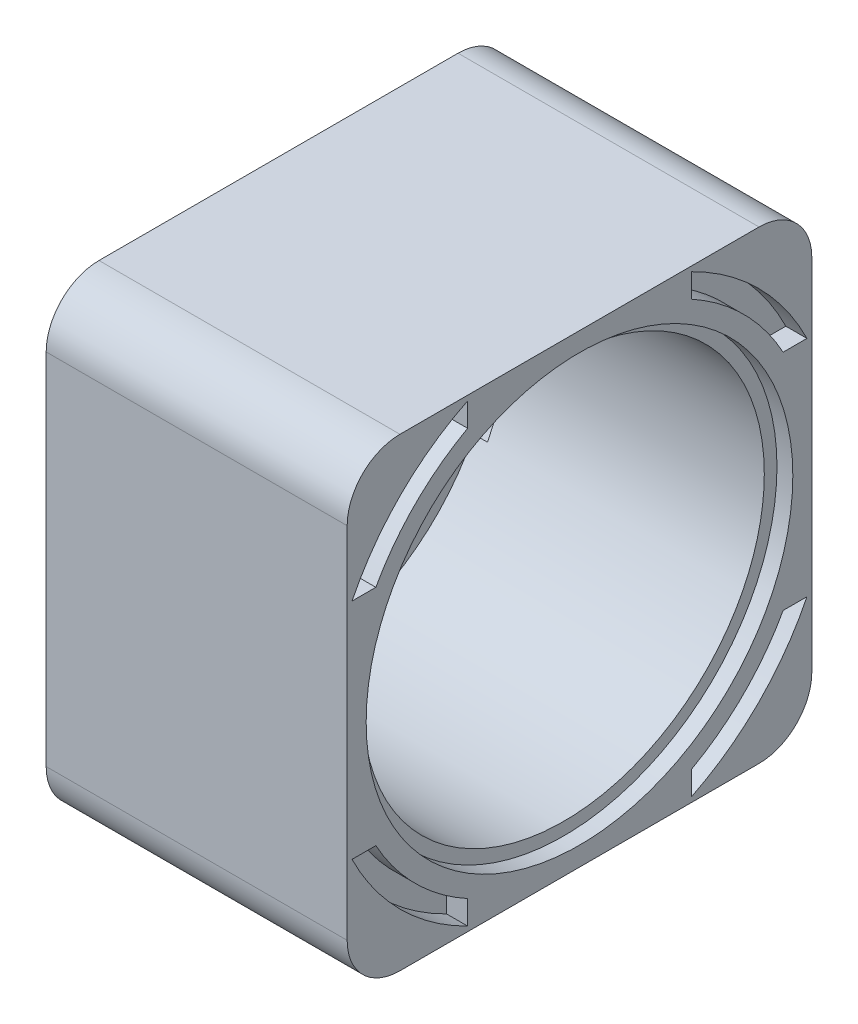
SolidWorks part; units mm, degrees
ref_plane "前视基准面" through (0, 0, 0) normal (0, 0, 1) x (1, 0, 0)
ref_plane "上视基准面" through (0, 0, 0) normal (0, 1, 0) x (1, 0, 0)
ref_plane "右视基准面" through (0, 0, 0) normal (1, 0, 0) x (0, 0, -1)
other "Configuration Table"
sketch "草图1" plane through (0, 0, 0) normal (1, 0, 0) x (0, 0, -1)
  line L6 (-22, 22) -> (22, 22)
  line L7 (-22, 22) -> (-22, -22)
  line L8 (-22, -22) -> (22, -22)
  line L9 (22, 22) -> (22, -22)
  line L10 (-22, 22) -> (22, -22) construction
  line L11 (-22, -22) -> (22, 22) construction
  point P0 (0, 0)
extrude "凸台-拉伸1" add sketch "草图1" along normal blind 1.5
sketch "草图2" plane through (1.5, 0, 0) normal (1, 0, 0) x (0, 0, -1)
  line L1 (0, 0) -> (5.5577, 0) construction
  circle A0 centre (0, 10.5) radius 1
  circle A1 centre (0, -10.5) radius 1
  circle A2 centre (0, -10.5) radius 2.5
  circle A5 centre (0, 10.5) radius 2.5
extrude "凸台-拉伸2" add sketch "草图2" along normal blind 3
sketch "草图3" plane through (1.5, 0, 0) normal (1, 0, 0) x (0, 0, -1)
  circle A0 centre (-12.5, -10.5) radius 2.5
  circle A1 centre (-12.5, -10.5) radius 1
  circle A2 centre (-12.5, 10.5) radius 1
  circle A3 centre (-12.5, 10.5) radius 2.5
extrude "凸台-拉伸3" add sketch "草图3" along normal blind 3.5
sketch "草图4" plane through (1.5, 0, 0) normal (1, 0, 0) x (0, 0, -1)
  line L5 (-22, 22) -> (22, 22)
  line L6 (-22, 22) -> (-22, -22)
  line L7 (-22, -22) -> (22, -22)
  line L8 (22, 22) -> (22, -22)
  line L9 (-22, 22) -> (22, -22) construction
  line L10 (-22, -22) -> (22, 22) construction
  circle A1 centre (0, 0) radius 19
extrude "凸台-拉伸4" add sketch "草图4" along normal blind 27
sketch "草图5" plane through (28.5, 0, 0) normal (1, 0, 0) x (0, 0, -1)
  circle A0 centre (0, 0) radius 20.2
  circle A1 centre (0, 0) radius 19
extrude "切除-拉伸1" cut sketch "草图5" against normal blind 1.5
sketch "草图6" plane through (28.5, 0, 0) normal (1, 0, 0) x (0, 0, -1)
  circle A0 centre (0, 0) radius 22
  circle A2 centre (0, 0) radius 20.2
extrude "凸台-拉伸5" [suppressed] add sketch "草图6" along normal blind 12
sketch "草图7" [suppressed] plane through (30.5, 0, 0) normal (1, 0, 0) x (0, 0, -1)
  line L0 (-15.6525, 14) -> (-16.9706, 14)
  line L1 (15.6525, 14) -> (16.9706, 14)
  line L2 (-15.6525, -14) -> (-16.9706, -14)
  line L3 (15.6525, -14) -> (16.9706, -14)
  line L4 (0, 0) -> (10.2642, 0) construction
  line L5 (1, -20.9762) -> (1, -21.9773)
  line L6 (1, 20.9762) -> (1, 21.9773)
  line L7 (-1, 20.9762) -> (-1, 21.9773)
  line L8 (-1, -20.9762) -> (-1, -21.9773)
  arc A0 (-15.6525, -14) -> (-1, -20.9762) centre (0, 0) ccw
  arc A1 (-16.9706, -14) -> (-1, -21.9773) centre (0, 0) ccw
  arc A2 (16.9706, 14) -> (1, 21.9773) centre (0, 0) ccw
  arc A3 (15.6525, 14) -> (1, 20.9762) centre (0, 0) ccw
  arc A4 (-1, 21.9773) -> (-16.9706, 14) centre (0, 0) ccw
  arc A5 (-1, 20.9762) -> (-15.6525, 14) centre (0, 0) ccw
  arc A6 (1, -21.9773) -> (16.9706, -14) centre (0, 0) ccw
  arc A7 (1, -20.9762) -> (15.6525, -14) centre (0, 0) ccw
extrude "凸台-拉伸6" [suppressed] add sketch "草图7" along normal blind 2
fillet "圆角2" radius 5 4 edges at (14.25, -22, 22) (14.25, -22, -22) (14.25, 22, -22) (14.25, 22, 22)
sketch "草图8" plane through (0, 0, 0) normal (0, 1, 0) x (1, 0, 0)
  line L0 (29.9095, 0) -> (0, 0) construction
  line L6 (17.0716, -9) -> (22.0716, -9)
  line L7 (17.0716, -9) -> (17.0716, 9)
  line L8 (17.0716, 9) -> (22.0716, 9)
  line L9 (22.0716, -9) -> (22.0716, 9)
  line L10 (17.0716, -9) -> (22.0716, 9) construction
  line L11 (17.0716, 9) -> (22.0716, -9) construction
  point P3 (19.5716, 0)
extrude "切除-拉伸3" [suppressed] cut sketch "草图8" against normal through all
pattern_circular "阵列(圆周)2" [suppressed] count 4 over 360 reverse direction yes of bodies 118
sketch "草图9" plane through (27, 0, 0) normal (1, 0, 0) x (0, 0, -1)
  circle A0 centre (0, 0) radius 20.7
extrude "切除-拉伸4" [suppressed] cut sketch "草图9" against normal blind 1 from offset 1.5
sketch "草图10" plane through (0, 0, 0) normal (0, 0, 1) x (1, 0, 0)
  line L0 (2.8, 8.5) -> (1.5, 8.5)
  line L1 (2.8, -8.5) -> (1.5, -8.5)
  line L3 (2.8, 8.5) -> (2.8, -8.5)
  line L4 (1.5, 8.5) -> (1.5, -8.5)
extrude "切除-拉伸5" cut sketch "草图10" against normal through all from offset 10 offset against normal yes
sketch "草图11" [suppressed] plane through (0, 0, 22) normal (0, 0, 1) x (1, 0, 0)
  line L0 (0, 0) -> (6.9999, 0) construction
  line L1 (6.9999, 0) -> (6.9999, 14) construction
  circle A0 centre (6.9999, 14) radius 2
  circle A1 centre (6.9999, -14) radius 2
extrude "切除-拉伸6" [suppressed] cut sketch "草图11" against normal blind 4
sketch "草图13" plane through (28.5, 0, 0) normal (1, 0, 0) x (0, 0, -1)
  line L9 (-10.5917, 21.5364) -> (-10.5917, 19.2825)
  line L21 (10.5917, 21.5364) -> (10.5917, 19.2825)
  line L22 (-21.5364, 10.5917) -> (-19.2825, 10.5917)
  line L23 (21.5364, 10.5917) -> (19.2825, 10.5917)
  line L24 (-21.5364, -10.5917) -> (-19.2825, -10.5917)
  line L25 (-10.5917, -21.5364) -> (-10.5917, -19.2825)
  line L26 (21.5364, -10.5917) -> (19.2825, -10.5917)
  line L27 (10.5917, -21.5364) -> (10.5917, -19.2825)
  arc A0 (-10.5917, 19.2825) -> (-19.2825, 10.5917) centre (0, 0) ccw
  arc A1 (-10.5917, 21.5364) -> (-21.5364, 10.5917) centre (0, 0) ccw
  arc A5 (19.2825, 10.5917) -> (10.5917, 19.2825) centre (0, 0) ccw
  arc A6 (21.5364, 10.5917) -> (10.5917, 21.5364) centre (0, 0) ccw
  arc A7 (10.5917, -19.2825) -> (19.2825, -10.5917) centre (0, 0) ccw
  arc A8 (10.5917, -21.5364) -> (21.5364, -10.5917) centre (0, 0) ccw
  arc A9 (-19.2825, -10.5917) -> (-10.5917, -19.2825) centre (0, 0) ccw
  arc A10 (-21.5364, -10.5917) -> (-10.5917, -21.5364) centre (0, 0) ccw
  dimension "D1" = 4
sketch "草图14" plane through (1.5, 0, 0) normal (1, 0, 0) x (0, 0, -1)
  line L2 (-11.7355, 13.6484) -> (11.7355, 13.6484)
  line L3 (-14.3091, 12.5) -> (14.3091, 12.5)
  arc A0 (16.9926, 8.5) -> (16.9926, -8.5) centre (0, 0) ccw construction
  arc A3 (11.7355, 13.6484) -> (-11.7355, 13.6484) centre (0, 0) ccw
  circle A4 centre (0, 0) radius 19 construction
  arc A5 (-14.3091, 12.5) -> (14.3091, 12.5) centre (0, 0) cw
extrude "凸台-拉伸9" [suppressed] add sketch "草图14" along normal blind 7
extrude "切除-拉伸7" cut sketch "草图13" against normal blind 2
